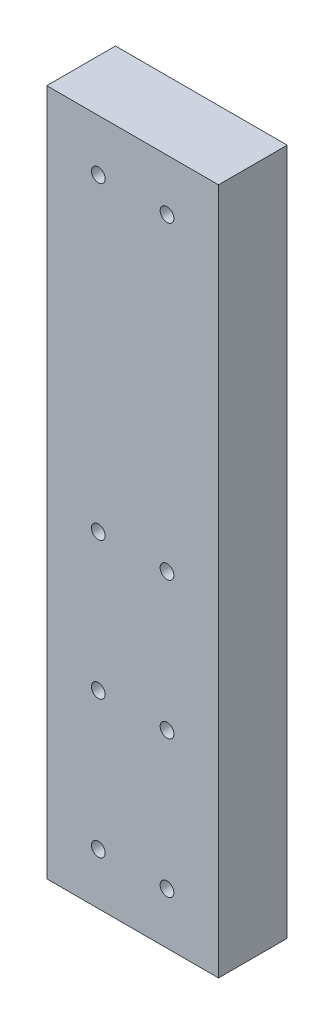
SolidWorks part; units mm, degrees
material "Mahogany"
ref_plane "Plan de face" through (0, 0, 0) normal (0, 0, 1) x (1, 0, 0)
ref_plane "Plan de dessus" through (0, 0, 0) normal (0, 1, 0) x (1, 0, 0)
ref_plane "Plan de droite" through (0, 0, 0) normal (1, 0, 0) x (0, 0, -1)
sketch "Sketch1" plane through (0, 0, 0) normal (0, 0, 1) x (1, 0, 0)
  line L1 (0, 0) -> (25, 0)
  line L2 (0, 0) -> (0, 100)
  line L3 (0, 100) -> (25, 100)
  line L4 (25, 0) -> (25, 100)
  dimension "D1" = 25
  dimension "D2" = 100
extrude "Boss-Extrude1" add sketch "Sketch1" along normal blind 10
sketch "Sketch2" plane through (0, 0, 10) normal (0, 0, 1) x (1, 0, 0)
  line L0 (12.5, 100) -> (12.5, 0) construction
  line L1 (25, 100) -> (0, 100) construction
  line L2 (0, 0) -> (25, 0) construction
  line L3 (7.5, 92.5) -> (7.5, 0) construction
  line L4 (0, 92.5) -> (25, 92.5) construction
  line L5 (0, 100) -> (0, 0) construction
  line L6 (25, 0) -> (25, 100) construction
  circle A0 centre (7.5, 92.5) radius 1
  circle A1 centre (7.5, 47.5) radius 1
  circle A2 centre (7.5, 27.5) radius 1
  circle A3 centre (7.5, 7.5) radius 1
  circle A4 centre (17.5, 92.5) radius 1
  circle A5 centre (17.5, 7.5) radius 1
  circle A6 centre (17.5, 27.5) radius 1
  circle A7 centre (17.5, 47.5) radius 1
  dimension "D1" = 2
  dimension "D2" = 2
  dimension "D3" = 2
  dimension "D4" = 20
  dimension "D5" = 45
  dimension "D6" = 5
  dimension "D8" = 2
  dimension "D7" = 7.5
  dimension "D9" = 20
extrude "Cut-Extrude1" cut sketch "Sketch2" against normal through all contours A0 | A7 | A1 | A6 | A2 | A5 | A3 | A4 region at (7.5, 92.5, 10) region at (7.5, 47.5, 10) region at (7.5, 27.5, 10) region at (7.5, 7.5, 10) region at (17.5, 7.5, 10) region at (17.5, 27.5, 10) region at (17.5, 47.5, 10)
